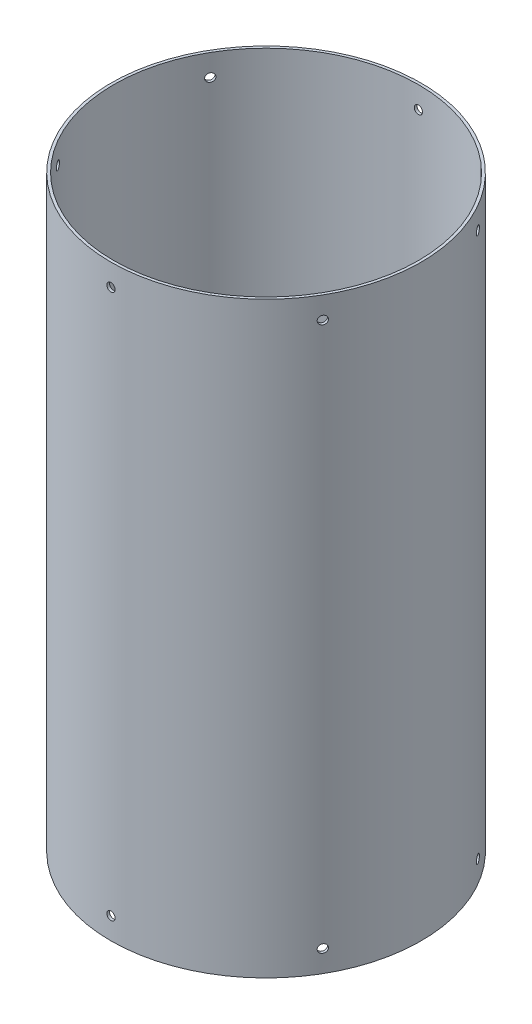
SolidWorks part; units mm, degrees
ref_plane "Front Plane" through (0, 0, 0) normal (0, 0, 1) x (1, 0, 0)
ref_plane "Top Plane" through (0, 0, 0) normal (0, 1, 0) x (1, 0, 0)
ref_plane "Right Plane" through (0, 0, 0) normal (1, 0, 0) x (0, 0, -1)
sketch "Sketch2" plane through (0, 0, 0) normal (0, 1, 0) x (1, 0, 0)
  circle A0 centre (0, 0) radius 88.9
  circle A1 centre (0, 0) radius 90.4875
  dimension "D1" = 177.8
  dimension "D2" = 1.5875
extrude "Boss-Extrude1" add sketch "Sketch2" along normal blind 342.9
sketch "Sketch3" plane through (0, 0, 0) normal (0, 0, 1) x (1, 0, 0)
  line L0 (0, 0) -> (0, 12.7) construction
  line L1 (-90.4875, 0) -> (90.4875, 0) construction
  line L2 (-90.4875, 0) -> (-90.4875, 342.9) construction
  line L3 (-90.4875, 342.9) -> (90.4875, 342.9) construction
  line L4 (90.4875, 0) -> (90.4875, 342.9) construction
  line L5 (0, 12.7) -> (0, 330.2) construction
  line L7 (0, 342.9) -> (0, 330.2) construction
  circle A0 centre (0, 330.2) radius 2.413
  circle A1 centre (0, 12.7) radius 2.413
  dimension "D2" = 4.826
  dimension "D4" = 4.826
  dimension "D1" = 12.7
  dimension "D3" = 12.7
extrude "Cut-Extrude1" cut sketch "Sketch3" against normal through all both and the other way through all
pattern_circular "CirPattern1" count 6 over 360 about axis through (0, 342.9, 0) along (0, 1, 0) of "Cut-Extrude1"
